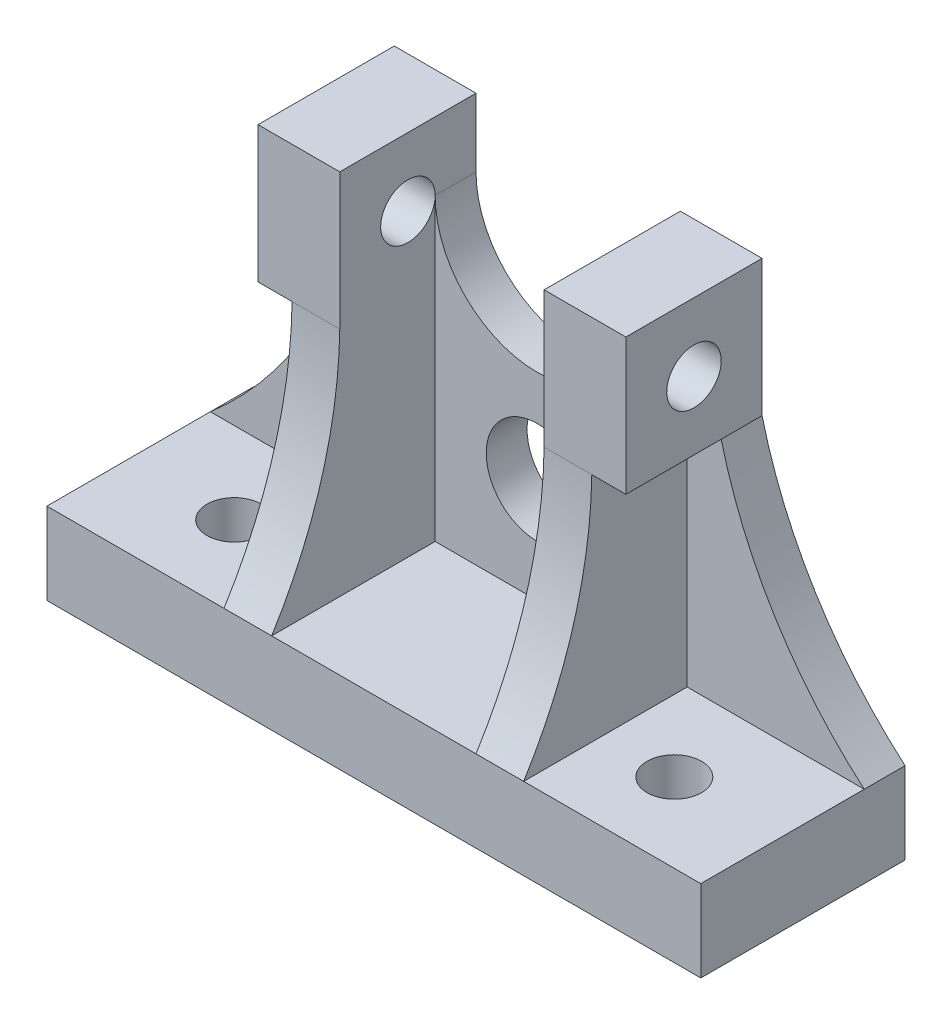
SolidWorks part; units mm, degrees
ref_plane "Front Plane" through (0, 0, 0) normal (0, 0, 1) x (1, 0, 0)
ref_plane "Top Plane" through (0, 0, 0) normal (0, 1, 0) x (1, 0, 0)
ref_plane "Right Plane" through (0, 0, 0) normal (1, 0, 0) x (0, 0, -1)
sketch "Sketch1" plane through (0, 0, 0) normal (0, 0, 1) x (1, 0, 0)
  line L0 (0, 0) -> (-13.0485, 0) construction
  line L1 (0, 0) -> (0, -28662.7551) construction
  line L2 (-27, 66) -> (-15, 66)
  line L3 (48, 12) -> (-48, 12)
  line L4 (48, 12) -> (48, 0)
  line L5 (48, 0) -> (-48, 0)
  line L6 (-48, 12) -> (-48, 0)
  line L7 (0, 0) -> (0, 12) construction
  line L8 (48, 6) -> (-48, 6) construction
  line L9 (15, 66) -> (27, 66)
  line L10 (-27, 66) -> (-27, 46)
  line L11 (27, 66) -> (27, 46)
  line L12 (-15, 66) -> (-15, 56)
  line L13 (15, 66) -> (15, 56)
  line L14 (-27, 46) -> (-15, 46)
  line L15 (-15, 46) -> (-15, 56)
  line L16 (27, 46) -> (15, 46)
  line L17 (15, 46) -> (15, 56)
  arc A1 (-48, 12) -> (-27, 46) centre (-91.0175, 62.0549) ccw
  arc A2 (48, 12) -> (27, 46) centre (91.0175, 62.0549) cw
  arc A3 (-15, 56) -> (15, 56) centre (0, 56) ccw
  circle A4 centre (0, 27) radius 7.5
  point P6 (0, 6)
  dimension "D5" = 10
  dimension "D7" = 132
  dimension "D8" = 12
  dimension "D9" = 15
  dimension "D1" = 96
  dimension "D2" = 12
  dimension "D3" = 54
  dimension "D4" = 66
  dimension "D6" = 20
  dimension "D10" = 15
extrude "Boss-Extrude1" add sketch "Sketch1" along normal blind 30 contours L3 L6 L5 L4 region at (0, 6, 0)
extrude "Boss-Extrude2" add sketch "Sketch1<3>" along normal blind 6 contours A3 L15 L14 A1 L3 A2 L16 L17 A4 region at (-21, 44.944, 0)
sketch "Sketch1<3>" plane through (0, 0, 0) normal (0, 0, 1) x (1, 0, 0) same geometry as "Sketch1"
extrude "Boss-Extrude3" add sketch "Sketch1<4>" along normal blind 20 contours L14 L15 L12 L2 L10 | L17 L16 L11 L9 L13 region at (-21, 56, 0) region at (21, 56, 0)
sketch "Sketch1<4>" plane through (0, 0, 0) normal (0, 0, 1) x (1, 0, 0) same geometry as "Sketch1"
sketch "Sketch2" plane through (-15, 0, 0) normal (1, 0, 0) x (0, 0, -1)
  line L0 (-30, 12) -> (-6, 12) construction
  line L2 (-20, 46) -> (-6, 46) construction
  line L4 (-20, 46) -> (-6, 46)
  line L5 (-6, 46) -> (-6, 12)
  line L6 (-6, 12) -> (-30, 12)
  arc A0 (-30, 12) -> (-20, 46) centre (-85.9933, 46.9392) ccw
  dimension "D1" = 66
extrude "Boss-Extrude4" add sketch "Sketch2" against normal blind 7
mirror "Mirror1" about plane through (0, 0, 0) normal (1, 0, 0) of "Boss-Extrude4"
hole_wizard "Ø8.0mm Dowel Hole1" positions "3DSketch2" profile "Sketch3" hole size "Ø8.0" standard "ANSI Metric" end condition through all
sketch3d "3DSketch2"
  line L0 (-27, 66, 20) -> (-27, 66, 0) construction
  line L1 (-27, 66, 0) -> (-27, 46, 0) construction
  point P0 (-27, 56, 10)
  dimension "D1" = 10
  dimension "D2" = 10
sketch "Sketch3" plane through (-27, 56, 10) normal (0, 1, 0) x (0, 0, 1)
  line L0 (0, 0) -> (0, 75)
  line L1 (0, 75) -> (4, 75)
  line L2 (4, 75) -> (4, 0)
  line L5 (4, 0) -> (0, 0)
  line L11 (0, -6.35) -> (0, 107.95) construction
  dimension "Thru Hole Dia." = 8
  dimension "Thru Hole Depth" = 75
hole_wizard "Ø8.0mm Dowel Hole2" positions "3DSketch3" profile "Sketch4" hole size "Ø8.0" standard "ANSI Metric" end condition through all
sketch3d "3DSketch3"
  line L1 (-48, 12, 30) -> (-48, 12, 6) construction
  line L2 (-22, 12, 30) -> (-48, 12, 30) construction
  point P0 (-32.5, 12, 18)
  point P2 (32.4989, 12, 18.3811)
  dimension "D1" = 65
  dimension "D2" = 15.5
  dimension "D3" = 12
sketch "Sketch4" plane through (-32.5, 12, 18) normal (1, 0, 0) x (0, 0, 1)
  line L0 (0, 0) -> (0, 12)
  line L1 (0, 12) -> (4, 12)
  line L2 (4, 12) -> (4, 0)
  line L5 (4, 0) -> (0, 0)
  line L11 (0, -6.35) -> (0, 107.95) construction
  dimension "Thru Hole Dia." = 8
  dimension "Thru Hole Depth" = 12
